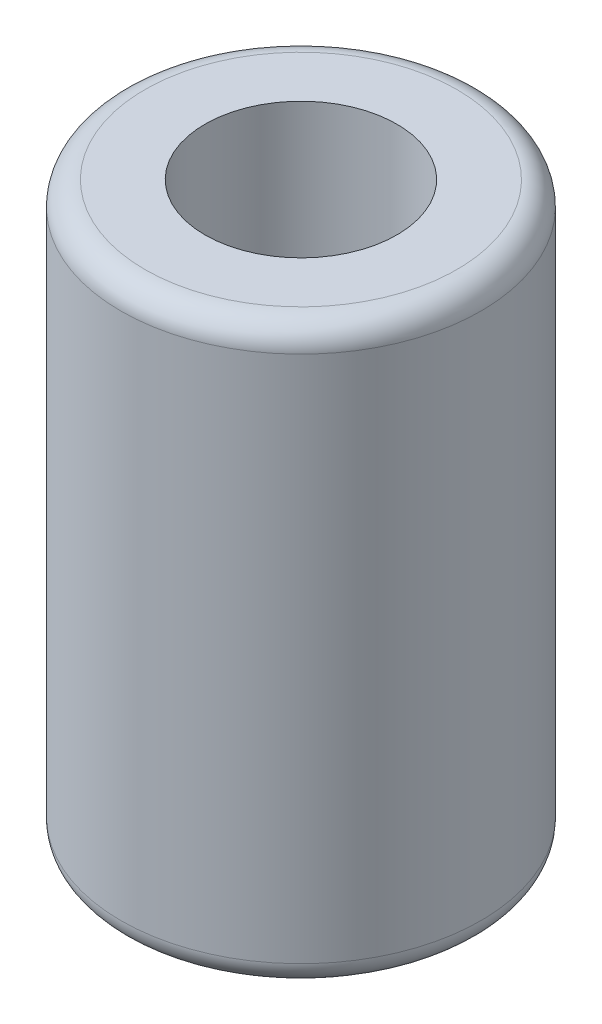
SolidWorks part; units mm, degrees
ref_plane "Front Plane" through (0, 0, 0) normal (0, 0, 1) x (1, 0, 0)
ref_plane "Top Plane" through (0, 0, 0) normal (0, 1, 0) x (1, 0, 0)
ref_plane "Right Plane" through (0, 0, 0) normal (1, 0, 0) x (0, 0, -1)
sketch "Sketch1" plane through (0, 0, 0) normal (0, 1, 0) x (1, 0, 0)
  circle A0 centre (0, 0) radius 4
  circle A1 centre (0, 0) radius 7.5
  dimension "D1" = 8
  dimension "D2" = 15
extrude "Boss-Extrude1" add sketch "Sketch1" along normal blind 12 and the other way blind 12
fillet "Fillet1" radius 1 2 edges at (0, -12, 7.5) (0, 12, 7.5)
ref_axis "Bearing Axis" through (0, -12, 0) along (0, 1, 0)
